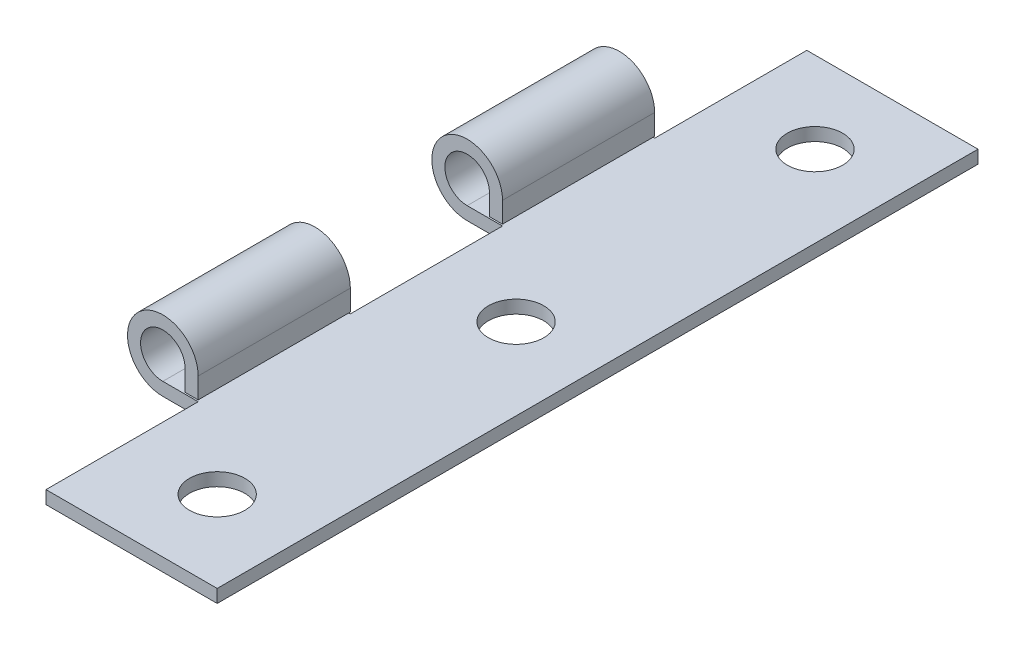
SolidWorks part; units mm, degrees
ref_plane "Front Plane" through (0, 0, 0) normal (0, 0, 1) x (1, 0, 0)
ref_plane "Top Plane" through (0, 0, 0) normal (0, 1, 0) x (1, 0, 0)
ref_plane "Right Plane" through (0, 0, 0) normal (1, 0, 0) x (0, 0, -1)
sketch "Sketch1" plane through (0, 0, 0) normal (0, 1, 0) x (1, 0, 0)
  line L0 (0, 28) -> (0, 42)
  line L1 (0, 0) -> (15.75, 0)
  line L2 (0, 0) -> (0, 14)
  line L3 (0, 70) -> (15.75, 70)
  line L4 (15.75, 0) -> (15.75, 70)
  line L5 (0, 14) -> (-1, 14)
  line L7 (0, 28) -> (-1, 28)
  line L8 (-1, 14) -> (-1, 28)
  line L9 (0, 56) -> (0, 70)
  line L10 (0, 56) -> (-1, 56)
  line L12 (0, 42) -> (-1, 42)
  line L13 (-1, 56) -> (-1, 42)
  circle A0 centre (8.25, 62.5) radius 2.55
  circle A1 centre (8.25, 35) radius 2.55
  circle A2 centre (8.25, 7.5) radius 2.55
  dimension "D9" = 5.1
  dimension "D10" = 5.1
  dimension "D11" = 5.1
  dimension "D13" = 7.5
  dimension "D14" = 7.5
  dimension "D16" = 55
  dimension "D17" = 7.5
  dimension "D1" = 70
  dimension "D2" = 15.75
  dimension "D3" = 14
  dimension "D4" = 14
  dimension "D5" = 1
  dimension "D6" = 14
  dimension "D7" = 14
  dimension "D8" = 1
  dimension "D12" = 7.5
  dimension "D15" = 35
base flange "Base-Flange1" sketch "Sketch1" thickness 1.2 reverse thickness direction no parameters "D1"=0.7366
sketch "Sketch10" plane through (0, 0, -42) normal (0, 0, 1) x (1, 0, 0)
  line L0 (0, -1.2) -> (0, 0) construction
  line L1 (-1, -1.2) -> (0, -1.2) construction
  line L2 (-3.25, -1.2) -> (-1, -1.2)
  line L3 (0, 2.05) -> (0, 0.1456)
  line L4 (-1.2, 2.05) -> (-1.2, 0.1456)
  line L5 (-1.2, 0.1456) -> (0, 0.1456)
  line L6 (0, 0) -> (-1, 0)
  line L7 (-1, 0) -> (-1, -1.2)
  line L8 (-1, -1.2) -> (0, -1.2)
  line L9 (0, -1.2) -> (0, 0)
  line L12 (-1, -1.2) -> (0, -1.2)
  line L13 (0, -1.2) -> (0, 0)
  line L14 (0, 0) -> (-3.25, 0)
  arc A0 (0, 2.05) -> (-3.25, -1.2) centre (-3.25, 2.05) ccw
  arc A1 (-1.2, 2.05) -> (-3.25, 0) centre (-3.25, 2.05) ccw
  dimension "D1" = 3.25
  dimension "D4" = 4.1
  dimension "D2" = 3.25
  dimension "D5" = 3.25
  dimension "D6" = 1.2
  dimension "D3" = 0
extrude "Boss-Extrude1" add sketch "Sketch10" against normal up to surface (14 mm away) up to face at (-0.5, -0.6, -56)
sketch "Sketch11" plane through (0, 0, -14) normal (0, 0, 1) x (1, 0, 0)
  line L0 (-1.2, 2.05) -> (-1.2, 0.1456)
  line L1 (-1.2, 0.1456) -> (0, 0.1456)
  line L2 (0, 0.1456) -> (0, 2.05)
  line L3 (0, 0) -> (-3.25, 0)
  line L4 (0, -1.2) -> (-3.25, -1.2)
  line L9 (0, 0) -> (-1, 0)
  line L10 (-1, 0) -> (-1, -1.2)
  line L11 (-1, -1.2) -> (0, -1.2)
  line L12 (0, -1.2) -> (0, 0)
  line L16 (0, -1.2) -> (0, 0)
  arc A0 (-1.2, 2.05) -> (-3.25, 0) centre (-3.25, 2.05) ccw
  arc A2 (0, 2.0492) -> (-3.25, -1.2) centre (-3.25, 2.05) ccw
  line M11 (-1, 0) -> (-1, -1.2)
  dimension "D2" = 3.25
  dimension "D1" = 0
extrude "Boss-Extrude2" add sketch "Sketch11" against normal blind 14 contours L2 A2 L4 L3 A0 L0 L1 M11
sketch "Sketch12" plane through (0, 0, 0) normal (0, 1, 0) x (1, 0, 0)
  line L0 (-25, 42) -> (-25, 56)
  line L1 (-25, 0) -> (-40.75, 0)
  line L2 (-25, 14) -> (-25, 28)
  line L3 (-25, 70) -> (-40.75, 70)
  line L4 (-40.75, 0) -> (-40.75, 70)
  line L5 (-25, 70) -> (-24, 70)
  line L7 (-25, 56) -> (-24, 56)
  line L8 (-24, 70) -> (-24, 56)
  line L9 (-25, 0) -> (-24, 0)
  line L11 (-25, 14) -> (-24, 14)
  line L12 (-24, 0) -> (-24, 14)
  line L13 (-25, 42) -> (-24, 42)
  line L15 (-25, 28) -> (-24, 28)
  line L16 (-24, 42) -> (-24, 28)
  line L17 (-32.875, 0) -> (-32.875, 70) construction
  circle A1 centre (-32.875, 35) radius 2.55
  circle A3 centre (-32.875, 7.5) radius 2.55
  circle A4 centre (-32.875, 62.5) radius 2.55
  dimension "D3" = 5.1
  dimension "D4" = 5.1
  dimension "D5" = 5.1
  dimension "D2" = 15.75
  dimension "D6" = 14
  dimension "D7" = 14
  dimension "D8" = 14
  dimension "D9" = 14
  dimension "D10" = 1
  dimension "D11" = 1
  dimension "D12" = 1
  dimension "D13" = 7.5
  dimension "D14" = 35
  dimension "D16" = 55
  dimension "D17" = 24
  dimension "D18" = 70
  dimension "D19" = 15.75
  dimension "D20" = 70
base flange "Base-Flange2" [suppressed] sketch "Sketch12" thickness 1.2 reverse thickness direction no parameters "D1"=0.7366
sketch "Sketch15" [suppressed] plane through (0, 0, -56) normal (0, 0, 1) x (1, 0, 0)
  line L4 (-24, 0) -> (-25, 0)
  line L5 (-25, 0) -> (-25, -1.2)
  line L6 (-25, -1.2) -> (-24, -1.2)
  line L7 (-24, -1.2) -> (-24, 0)
  line L8 (-24, 0) -> (-25, 0)
  line L9 (-25, 0) -> (-25, -1.2)
  line L10 (-25, -1.2) -> (-24, -1.2)
  line L12 (-23.8, 0.15) -> (-25, 0.15)
  line L13 (-24, -1.2) -> (-21.75, -1.2)
  line L14 (-24, 0) -> (-21.75, 0)
  line L15 (-25, 2.05) -> (-25, 0.15)
  line L16 (-23.8, 2.05) -> (-23.8, 0.15)
  arc A0 (-21.75, -1.2) -> (-25, 2.05) centre (-21.75, 2.05) ccw
  arc A1 (-21.75, 0) -> (-23.8, 2.05) centre (-21.75, 2.05) ccw
  dimension "D4" = 6.5
  dimension "D5" = 4.1
  dimension "D2" = 3.25
  dimension "D3" = 3.25
  dimension "D1" = 0
extrude "Boss-Extrude3" [suppressed] add sketch "Sketch15" against normal up to surface (14 mm away)
sketch "Sketch16" [suppressed] plane through (0, 0, -28) normal (0, 0, 1) x (1, 0, 0)
  line L1 (-25, -1.2) -> (-25, 0) construction
  line L3 (-24, 0) -> (-21.75, 0)
  line L5 (-23.8, 2.05) -> (-23.8, 0.15)
  line L6 (-24, 0) -> (-25, 0)
  line L7 (-25, 0) -> (-25, -1.2)
  line L8 (-25, -1.2) -> (-24, -1.2)
  line L9 (-24, -1.2) -> (-24, 0)
  line L10 (-24, 0) -> (-25, 0)
  line L11 (-25, 0) -> (-25, -1.2)
  line L12 (-25, -1.2) -> (-24, -1.2)
  line L14 (-23.8, 0.15) -> (-25, 0.15)
  line L15 (-24, -1.2) -> (-21.75, -1.2)
  line L16 (-25, 2.05) -> (-25, 0.15)
  arc A0 (-21.75, -1.2) -> (-25, 2.05) centre (-21.75, 2.05) ccw
  arc A1 (-21.75, 0) -> (-23.8, 2.05) centre (-21.75, 2.05) ccw
  dimension "D1" = 6.5
  dimension "D4" = 4.1
  dimension "D3" = 3.25
  dimension "D7" = 2.25
  dimension "D5" = 0
sketch "Sketch18" [suppressed] plane through (0, 0, -14) normal (0, 0, -1) x (-1, 0, 0)
  line L1 (21.75, 0) -> (24, 0)
  line L4 (25, 0) -> (24, 0)
  line L5 (24, 0) -> (24, -1.2)
  line L6 (24, -1.2) -> (25, -1.2)
  line L7 (25, -1.2) -> (25, 0)
  line L8 (25, 0) -> (24, 0)
  line L10 (24, -1.2) -> (25, -1.2)
  line L11 (25, -1.2) -> (25, 0)
  line L13 (24, -1.2) -> (21.75, -1.2)
  line L15 (23.8, 2.05) -> (23.8, 0.15)
  line L16 (23.8, 0.15) -> (25, 0.15)
  line L17 (25, 0.15) -> (25, 2.05)
  arc A0 (23.8, 2.05) -> (21.75, 0) centre (21.75, 2.05) ccw
  arc A1 (25, 2.05) -> (21.75, -1.2) centre (21.75, 2.05) ccw
  dimension "D2" = 4.1
  dimension "D3" = 6.5
  dimension "D4" = 1.9
  dimension "D5" = 2.25
  dimension "D1" = 0
extrude "Boss-Extrude8" [suppressed] add sketch "Sketch16" against normal up to surface (14 mm away)
extrude "Boss-Extrude5" [suppressed] add sketch "Sketch18" against normal up to surface (14 mm away)
sketch "Sketch19" plane through (0, 0, 0) normal (0, 1, 0) x (1, 0, 0)
  circle A0 centre (-15.3371, 61.599) radius 2.05
  dimension "D1" = 4.1
extrude "Boss-Extrude6" [suppressed] add sketch "Sketch19" along normal blind 70 separate body
sketch "Sketch20" [suppressed] plane through (0, 70, 0) normal (0, 1, 0) x (1, 0, 0)
  circle A0 centre (-15.3371, 61.599) radius 3.2
  dimension "D2" = 6.4
extrude "Boss-Extrude7" [suppressed] add sketch "Sketch20" along normal blind 2
sketch "Bend-Lines1" [suppressed] plane through (0, 0, 0) normal (0, 1, 0) x (1, 0, 0)
sketch "Bounding-Box1" [suppressed] plane through (0, 0, 0) normal (0, 1, 0) x (1, 0, 0)
sheet metal parameters "Sheet-Metal1" thickness 1.2 parameters "D1"=0.7366
flat pattern "Flat-Pattern1" [suppressed]
sketch "Bend-Lines2" plane through (0, 0, 0) normal (0, 1, 0) x (1, 0, 0)
sketch3d "Bounding-Box2" [suppressed]
  line L0 (-1, 70, 0) -> (-1, 0, 0) construction
  line L1 (15.75, 70, 0) -> (15.75, 0, 0) construction
  line L2 (-1, 70, 0) -> (15.75, 70, 0) construction
  line L3 (-1, 0, 0) -> (15.75, 0, 0) construction
sheet metal parameters "Sheet-Metal2" thickness 1.2 parameters "D1"=0.7366
flat pattern "Flat-Pattern1"
sketch "Bend-Lines2" plane through (0, 0, 0) normal (0, 1, 0) x (1, 0, 0)
sketch3d "Bounding-Box2" [suppressed]
  line L0 (-3.25, 70, 0) -> (-3.25, 0, 0) construction
  line L1 (15.75, 70, 0) -> (15.75, 0, 0) construction
  line L2 (-3.25, 70, 0) -> (15.75, 70, 0) construction
  line L3 (-3.25, 0, 0) -> (15.75, 0, 0) construction
sheet metal parameters "Sheet-Metal3" thickness 1.2 parameters "D1"=0.7366
flat pattern "Flat-Pattern1"
sketch "Bend-Lines2" plane through (0, 0, 0) normal (0, 1, 0) x (1, 0, 0)
sketch3d "Bounding-Box2" [suppressed]
  line L0 (-3.25, 70, 0) -> (-3.25, 0, 0) construction
  line L1 (15.75, 70, 0) -> (15.75, 0, 0) construction
  line L2 (-3.25, 70, 0) -> (15.75, 70, 0) construction
  line L3 (-3.25, 0, 0) -> (15.75, 0, 0) construction
sheet metal parameters "Sheet-Metal4" thickness 1.2 parameters "D1"=0.7366
flat pattern "Flat-Pattern4"
sketch "Bend-Lines3" plane through (0, 0, 0) normal (0, 1, 0) x (1, 0, 0)
sketch3d "Bounding-Box3" [suppressed]
  line L0 (-40.75, 70, 0) -> (-40.75, 0, 0) construction
  line L1 (-24, 70, 0) -> (-24, 0, 0) construction
  line L2 (-40.75, 70, 0) -> (-24, 70, 0) construction
  line L3 (-40.75, 0, 0) -> (-24, 0, 0) construction
sheet metal parameters "Sheet-Metal5" thickness 1.2 parameters "D1"=0.7366
flat pattern "Flat-Pattern4"
sketch "Bend-Lines3" plane through (0, 0, 0) normal (0, 1, 0) x (1, 0, 0)
sketch3d "Bounding-Box3" [suppressed]
  line L0 (-40.75, 70, 0) -> (-40.75, 0, 0) construction
  line L1 (-21.75, 70, 0) -> (-21.75, 0, 0) construction
  line L2 (-40.75, 70, 0) -> (-21.75, 70, 0) construction
  line L3 (-40.75, 0, 0) -> (-21.75, 0, 0) construction
sheet metal parameters "Sheet-Metal7" thickness 1.2 parameters "D1"=0.7366
flat pattern "Flat-Pattern4"
sketch "Bend-Lines3" plane through (0, 0, 0) normal (0, 1, 0) x (1, 0, 0)
sketch3d "Bounding-Box3" [suppressed]
  line L0 (-40.75, 70, 0) -> (-40.75, 0, 0) construction
  line L1 (-21.75, 70, 0) -> (-21.75, 0, 0) construction
  line L2 (-40.75, 70, 0) -> (-21.75, 70, 0) construction
  line L3 (-40.75, 0, 0) -> (-21.75, 0, 0) construction
sheet metal parameters "Sheet-Metal10" [suppressed] thickness 1.2 parameters "D1"=0.7366
flat pattern "Flat-Pattern4"
sketch "Bend-Lines3" plane through (0, 0, 0) normal (0, 1, 0) x (1, 0, 0)
sketch3d "Bounding-Box3" [suppressed]
  line L0 (-40.75, 70, 0) -> (-40.75, 0, 0) construction
  line L1 (-21.75, 70, 0) -> (-21.75, 0, 0) construction
  line L2 (-40.75, 70, 0) -> (-21.75, 70, 0) construction
  line L3 (-40.75, 0, 0) -> (-21.75, 0, 0) construction
